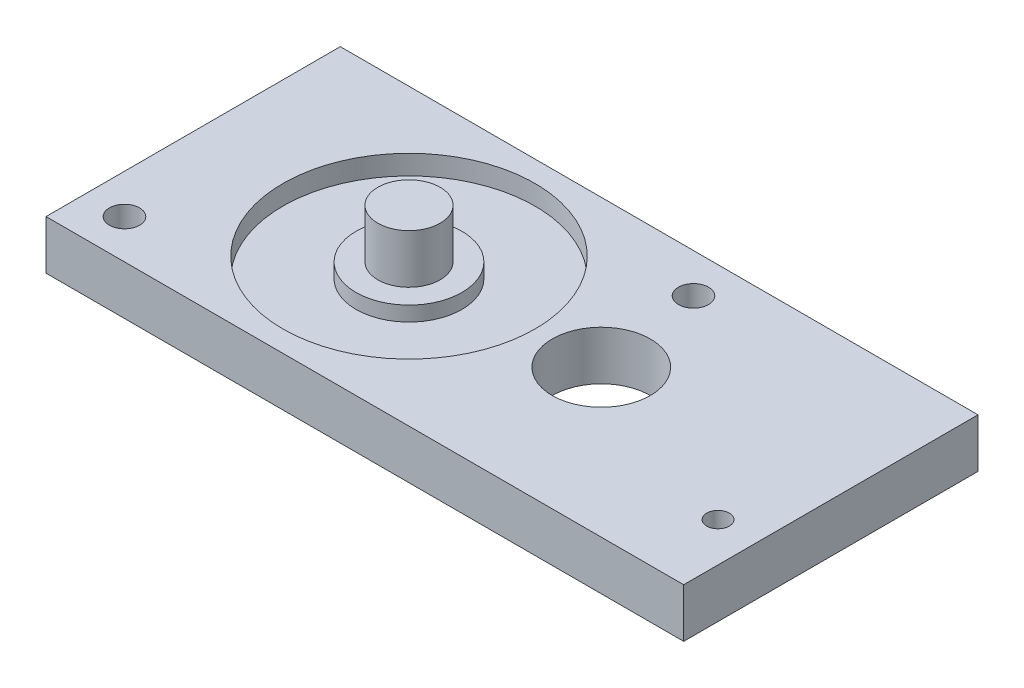
SolidWorks part; units mm, degrees
ref_plane "Front" through (0, 0, 0) normal (0, 0, 1) x (1, 0, 0)
ref_plane "Top" through (0, 0, 0) normal (0, 1, 0) x (1, 0, 0)
ref_plane "Right" through (0, 0, 0) normal (1, 0, 0) x (0, 0, -1)
sketch "Sketch1" plane through (0, 0, 0) normal (0, 1, 0) x (1, 0, 0)
  line L0 (-22, -15) -> (35, -15)
  line L1 (-22, 15) -> (35, 15)
  line L2 (-22, 15) -> (-22, -15)
  line L3 (35, 15) -> (35, -15)
  dimension "D1" = 30
extrude "Boss-Extrude1" add sketch "Sketch1" along normal blind 5
sketch "Sketch2" plane through (0, 5, 0) normal (0, 1, 0) x (1, 0, 0)
  circle A0 centre (0, 0) radius 3.175
  dimension "D1" = 6.35
extrude "Boss-Extrude2" add sketch "Sketch2" along normal blind 4.5
sketch "Sketch3" plane through (0, 5, 0) normal (0, 1, 0) x (1, 0, 0)
  circle A0 centre (-18, -11) radius 1.5367
  circle A1 centre (18, 11) radius 1.5367
  dimension "D5" = 3.0734
  dimension "D1" = 18
  dimension "D2" = 11
  dimension "D3" = 11
  dimension "D4" = 18
extrude "Cut-Extrude1" cut sketch "Sketch3" against normal blind 5
sketch "Sketch4" plane through (0, 5, 0) normal (0, 1, 0) x (1, 0, 0)
  circle A0 centre (0, 0) radius 5.4
  circle A1 centre (0, 0) radius 12.85
  dimension "D1" = 25.7
  dimension "D2" = 10.8
extrude "Cut-Extrude2" cut sketch "Sketch4" against normal blind 2
sketch "Sketch5" plane through (0, 5, 0) normal (0, 1, 0) x (1, 0, 0)
  circle A0 centre (19.6, 0) radius 5
  dimension "D2" = 10
  dimension "D1" = 19.6
extrude "Cut-Extrude3" cut sketch "Sketch5" against normal blind 10
sketch "Sketch6" plane through (0, 5, 0) normal (0, 1, 0) x (1, 0, 0)
  line L0 (-22, -15) -> (35, -15) construction
  line L1 (35, 15) -> (43, 15)
  line L2 (35, 15) -> (35, -15)
  line L3 (35, -15) -> (43, -15)
  line L4 (43, 15) -> (43, -15)
  dimension "D1" = 8
extrude "Boss-Extrude3" add sketch "Sketch6" against normal blind 5
sketch "Sketch7" plane through (0, 5, 0) normal (0, 1, 0) x (1, 0, 0)
  circle A0 centre (0, 0) radius 3.175
  circle A1 centre (0, 0) radius 5.4
  circle A2 centre (0, 0) radius 5.4 construction
  circle A3 centre (0, 0) radius 3.175 construction
extrude "Cut-Extrude4" cut sketch "Sketch7" against normal blind 0.5
sketch "Sketch8" plane through (0, 5, 0) normal (0, 1, 0) x (1, 0, 0)
  line L0 (-22, -15) -> (43, -15) construction
  line L1 (43, -15) -> (43, 15) construction
  circle A0 centre (39, -7.5) radius 1.15
  dimension "D1" = 2.3
  dimension "D2" = 7.5
  dimension "D3" = 4
extrude "Cut-Extrude5" cut sketch "Sketch8" against normal blind 15
